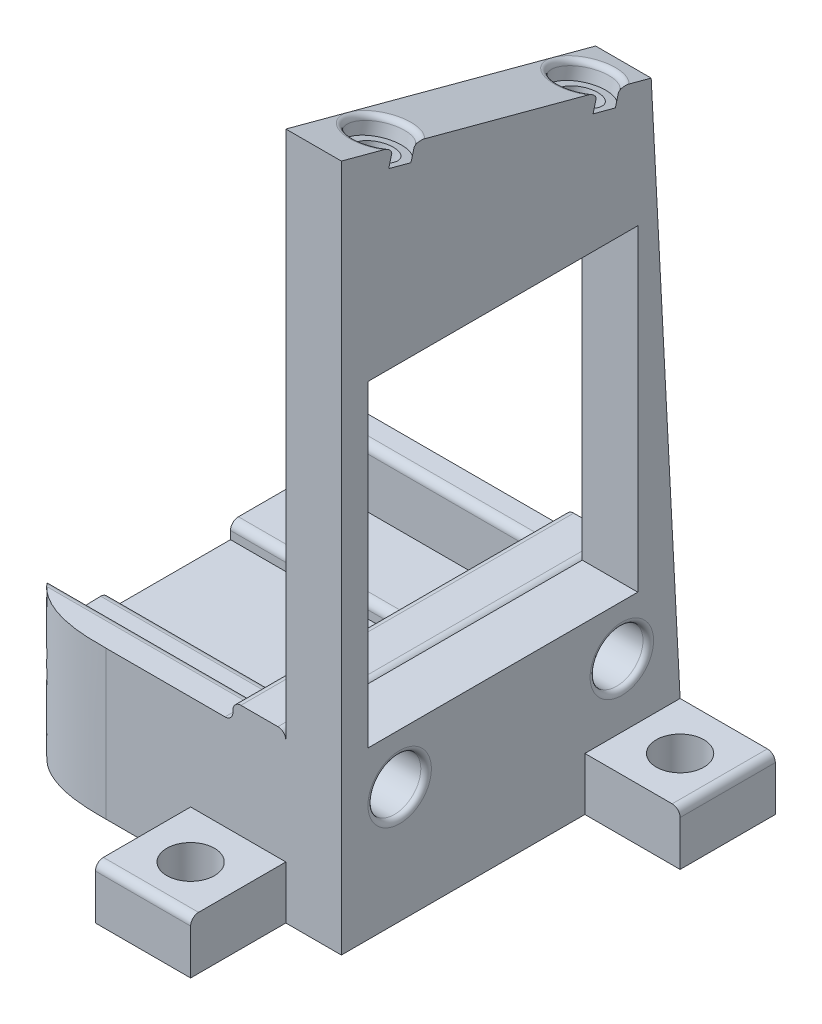
SolidWorks part; units mm, degrees
ref_plane "Front" through (0, 0, 0) normal (0, 0, 1) x (1, 0, 0)
ref_plane "Top" through (0, 0, 0) normal (0, 1, 0) x (1, 0, 0)
ref_plane "Right" through (0, 0, 0) normal (1, 0, 0) x (0, 0, -1)
sketch "Sketch1" plane through (0, 0, 0) normal (1, 0, 0) x (0, 0, -1)
  line L0 (-13.0089, 0) -> (13.0089, 0)
  line L1 (13.0089, 0) -> (13.0089, 8.5)
  line L2 (13.0089, 8.5) -> (5.7589, 8.5)
  line L3 (5.7589, 8.5) -> (5.7589, 7)
  line L4 (5.7589, 7) -> (-5.7589, 7)
  line L5 (-5.7589, 7) -> (-5.7589, 8.5)
  line L6 (-5.7589, 8.5) -> (-13.0089, 8.5)
  line L7 (-13.0089, 8.5) -> (-13.0089, 0)
  dimension "D1" = 8.5
  dimension "D2" = 7.25
  dimension "D3" = 26.0178
  dimension "D4" = 1.5
extrude "Boss-Extrude1" add sketch "Sketch1" along normal mid plane 22
sketch "Sketch3" plane through (0, 0, 0) normal (0, -1, 0) x (1, 0, 0)
  line L1 (-11, -13.0089) -> (11, -13.0089)
  line L2 (-11, -13.0089) -> (-11, -16.0089)
  line L3 (-11, -16.0089) -> (11, -16.0089)
  line L4 (11, -13.0089) -> (11, -16.0089)
  line L5 (-11, 13.0089) -> (11, 13.0089)
  line L6 (-11, 13.0089) -> (-11, 16.0089)
  line L7 (-11, 16.0089) -> (11, 16.0089)
  line L8 (11, 13.0089) -> (11, 16.0089)
  dimension "D1" = 3
  dimension "D2" = 22
  dimension "D3" = 3
  dimension "D4" = 22
extrude "Boss-Extrude2" add sketch "Sketch3" against normal blind 14
sketch "Sketch4" plane through (11, 0, 0) normal (1, 0, 0) x (0, 0, -1)
  line L0 (0, 0) -> (0, 15.7) construction
  line L1 (-16.0089, 0) -> (16.0089, 0) construction
  line L2 (-8.8, 15.7) -> (-16.0089, 15.7)
  line L3 (-16.0089, 14) -> (-16.0089, 0) construction
  line L4 (-16.0089, 15.7) -> (-16.0089, 0)
  line L5 (-16.0089, 0) -> (16.0089, 0)
  line L6 (16.0089, 0) -> (16.0089, 15.7)
  line L7 (16.0089, 14) -> (16.0089, 0) construction
  line L8 (16.0089, 15.7) -> (-8.8, 15.7)
  dimension "D2" = 15.7
extrude "Boss-Extrude3" add sketch "Sketch4" along normal blind 5
sketch "Sketch5" plane through (16, 0, 0) normal (1, 0, 0) x (0, 0, -1)
  line L0 (-16.0089, 11) -> (-10.5, 11) construction
  line L1 (-16.0089, 15.7) -> (-16.0089, 0) construction
  line L2 (-10.5, 11) -> (-10.5, 0) construction
  line L3 (-16.0089, 0) -> (16.0089, 0) construction
  line L4 (0, 0) -> (0, 15.7) construction
  line L5 (16.0089, 15.7) -> (-16.0089, 15.7) construction
  circle A0 centre (-10.5, 11) radius 1.75
  circle A1 centre (10.5, 11) radius 1.75
  dimension "D3" = 3.5
  dimension "D1" = 5.5089
  dimension "D2" = 11
extrude "Cut-Extrude1" cut sketch "Sketch5" against normal through all
sketch "Sketch6" plane through (0, 0, 0) normal (0, -1, 0) x (1, 0, 0)
  line L5 (16, 25.0089) -> (7, 25.0089)
  line L13 (16, 25.0089) -> (16, 16.0089)
  line L14 (16, 16.0089) -> (7, 16.0089)
  line L23 (7, 25.0089) -> (7, 16.0089)
  dimension "D1" = 9
  dimension "D2" = 9
extrude "Boss-Extrude4" add sketch "Sketch6" against normal blind 5
sketch "Sketch10" plane through (0, 0, 0) normal (0, -1, 0) x (1, 0, 0)
  line L7 (11.5, 20.5089) -> (7, 20.5089) construction
  line L8 (7, 25.0089) -> (7, 16.0089) construction
  line L9 (11.5, 20.5089) -> (11.5, 16.0089) construction
  line L10 (16, 16.0089) -> (7, 16.0089) construction
  circle A1 centre (11.5, 20.5089) radius 2.25
  dimension "D1" = 4.5
extrude "Cut-Extrude2" cut sketch "Sketch10" against normal through all
fillet "Fillet1" radius 0.75 11 edges at (0, 8.5, 5.7589) (0, 8.5, -5.7589) (11, 11.25, 13.0089) (11, 11.25, -13.0089) (0, 14, 13.0089) (0, 14, -13.0089) (11, 15.7, 0) (11, 14, 14.5089) (11, 14, -14.5089) (16, 15.7, 0) (11.5, 5, 25.0089)
fillet "Fillet2" radius 10 1 edges at (-11, 7, 16.0089) curvature continuous yes
sketch "Sketch12" plane through (0, 0, 0) normal (0, -1, 0) x (1, 0, 0)
  line L1 (25, -16.0089) -> (16, -16.0089)
  line L2 (25, -16.0089) -> (25, 16.0089)
  line L3 (25, 16.0089) -> (16, 16.0089)
  line L4 (16, -16.0089) -> (16, 16.0089)
  dimension "D1" = 9
extrude "Boss-Extrude5" add sketch "Sketch12" against normal blind 65
sketch "Sketch13" plane through (25, 0, 0) normal (1, 0, 0) x (0, 0, -1)
  line L4 (16.0089, 65) -> (-16.0089, 65)
  line L5 (-16.0089, 65) -> (16.0089, 56.4209)
  line L6 (16.0089, 65) -> (16.0089, 0) construction
  line L7 (16.0089, 56.4209) -> (16.0089, 65)
  dimension "D1" = 15
extrude "Cut-Extrude4" cut sketch "Sketch13" against normal up to surface (9 mm away) up to face at (16, 39.975, 0)
sketch "Sketch14" plane through (25, 0, 0) normal (1, 0, 0) x (0, 0, -1)
  circle A0 centre (-10.5, 11) radius 2.5
  circle A1 centre (10.5, 11) radius 2.5
  dimension "D1" = 5
extrude "Cut-Extrude5" cut sketch "Sketch14" against normal blind 9.75
sketch "Sketch15" plane through (0, 56.6436, -15.1776) normal (0, 0.9659, -0.2588) x (1, 0, 0)
  line L0 (19, 0.8606) -> (19, -6.1394) construction
  line L2 (19, -6.1394) -> (16, -6.1394) construction
  line L3 (16, 0) -> (16, -4.0635) construction
  line L4 (16, 0.8606) -> (25, 0.8606) construction
  line L5 (19, -6.1394) -> (19, -26.1394) construction
  circle A0 centre (19, -6.1394) radius 1.7
  circle A1 centre (19, -26.1394) radius 1.7
  dimension "D4" = 3.4
  dimension "D1" = 3
  dimension "D2" = 7
  dimension "D3" = 20
extrude "Cut-Extrude6" cut sketch "Sketch15" against normal blind 5
sketch "Sketch16" plane through (0, 56.6436, -15.1776) normal (0, 0.9659, -0.2588) x (1, 0, 0)
  circle A0 centre (19, -6.1394) radius 2.5
  circle A1 centre (19, -26.1394) radius 2.5
  dimension "D1" = 5
extrude "Cut-Extrude7" cut sketch "Sketch16" against normal blind 1.6
fillet "Fillet3" radius 0.5 2 edges at (19, 58.8796, -6.8326) (19, 64.056, 12.4859)
fillet "Fillet4" radius 0.5 2 edges at (25, 11, -13) (25, 11, 8)
ref_plane "Plane1" through (0, 65, 0) normal (0, -1, 0) x (-1, 0, 0)
sketch "Sketch17" plane through (0, 65, 0) normal (0, -1, 0) x (-1, 0, 0)
  line L0 (-25, -16.0089) -> (-16, -16.0089) construction
  line L1 (-25, 16.0089) -> (-21.25, 16.0089)
  line L2 (-25, 16.0089) -> (-25, -16.0089)
  line L3 (-25, -16.0089) -> (-21.25, -16.0089)
  line L4 (-21.25, 16.0089) -> (-21.25, -16.0089)
  dimension "D1" = 3.75
extrude "Cut-Extrude9" cut sketch "Sketch17" along normal through all
fillet "Fillet5" radius 0.5 2 edges at (21.25, 11, -13) (21.25, 11, 8)
sketch "Sketch18" plane through (0, 0, 0) normal (0, -1, 0) x (1, 0, 0)
  line L1 (21.25, -16.0089) -> (30.25, -16.0089)
  line L2 (21.25, -16.0089) -> (21.25, -7.0089)
  line L3 (21.25, -7.0089) -> (30.25, -7.0089)
  line L4 (30.25, -16.0089) -> (30.25, -7.0089)
  dimension "D1" = 9
  dimension "D2" = 9
extrude "Boss-Extrude6" add sketch "Sketch18" against normal blind 5
sketch "Sketch19" plane through (0, 5, 0) normal (0, 1, 0) x (1, 0, 0)
  line L0 (21.25, 11.5089) -> (30.25, 11.5089) construction
  line L1 (21.25, 7.0089) -> (21.25, 16.0089) construction
  line L2 (30.25, 16.0089) -> (30.25, 7.0089) construction
  line L3 (25.75, 7.0089) -> (25.75, 16.0089) construction
  line L4 (30.25, 7.0089) -> (21.25, 7.0089) construction
  line L5 (21.25, 16.0089) -> (30.25, 16.0089) construction
  circle A0 centre (25.75, 11.5089) radius 2.25
  dimension "D1" = 4.5
extrude "Cut-Extrude10" cut sketch "Sketch19" against normal up to next
fillet "Fillet6" radius 0.75 1 edges at (30.25, 5, -11.5089)
sketch "Sketch20" plane through (16, 0, 0) normal (-1, 0, 0) x (0, 0, 1)
  line L0 (-12.0089, 45.7) -> (13.4911, 45.7)
  line L1 (13.4911, 45.7) -> (13.4911, 15.7)
  line L2 (13.4911, 15.7) -> (-12.0089, 15.7)
  line L3 (-12.0089, 15.7) -> (-12.0089, 45.7)
  line L4 (-16.0089, 56.4209) -> (-16.0089, 14.95) construction
  line L5 (-16.0089, 15.7) -> (16.0089, 15.7) construction
  point P6 (-16.0089, 35.6854)
  dimension "D1" = 25.5
  dimension "D2" = 30
  dimension "D3" = 4
extrude "Cut-Extrude11" cut sketch "Sketch20" against normal up to next
sketch "Sketch21" plane through (21.25, 0, 0) normal (1, 0, 0) x (0, 0, -1)
  line L0 (16.0089, 5) -> (16.0089, 56.4209)
  line L1 (16.0089, 56.4209) -> (13.2757, 57.1532)
  line L3 (13.2757, 57.1532) -> (16.0089, 5)
  line L5 (16.0089, 56.4209) -> (11.1641, 57.719) construction
  point P4 (13.5865, 57.0699)
  point P6 (0, 0)
  dimension "D1" = 3
extrude "Cut-Extrude12" cut sketch "Sketch21" against normal through all
